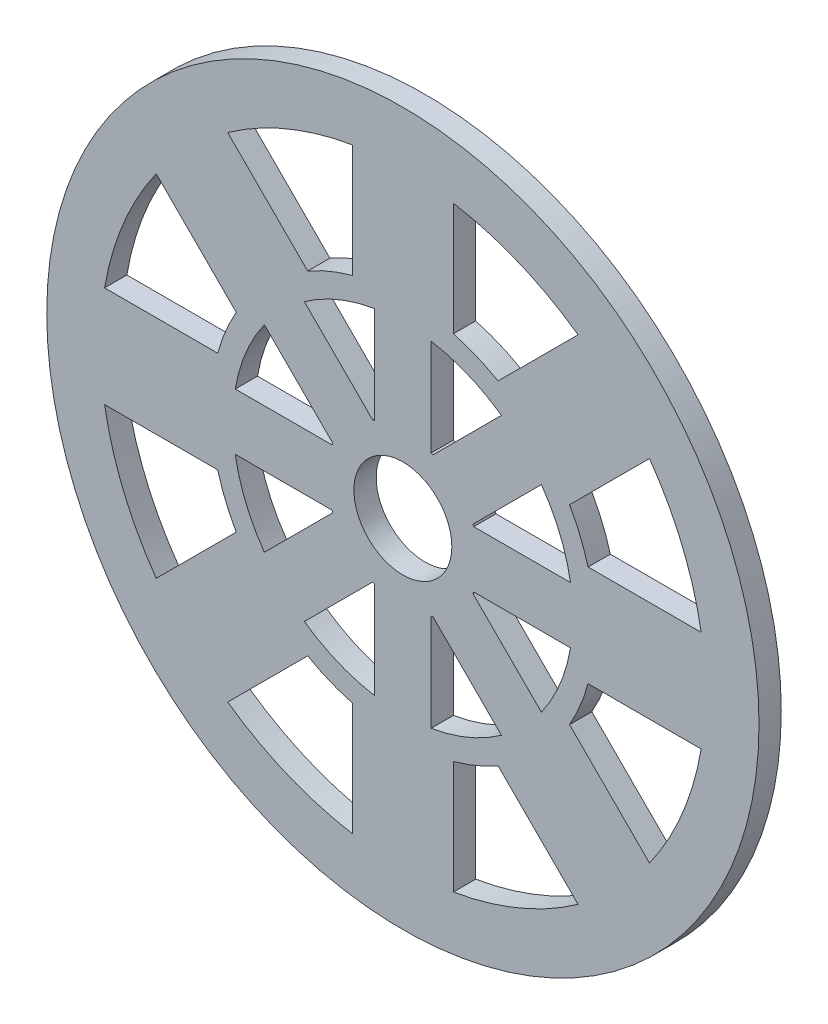
SolidWorks part; units mm, degrees
ref_plane "Front Plane" through (0, 0, 0) normal (0, 0, 1) x (1, 0, 0)
ref_plane "Top Plane" through (0, 0, 0) normal (0, 1, 0) x (1, 0, 0)
ref_plane "Right Plane" through (0, 0, 0) normal (1, 0, 0) x (0, 0, -1)
sketch "Sketch1" plane through (0, 0, 0) normal (0, 0, 1) x (1, 0, 0)
  line L0 (0, 80) -> (0, -80) construction
  line L1 (80, 0) -> (-80, 0) construction
  line L2 (33.9058, -24.9255) -> (51.8663, -42.886)
  line L3 (41.6, -6.35) -> (67, -6.35)
  line L4 (41.6, -6.35) -> (41.6, 6.35)
  line L5 (41.6, 6.35) -> (67, 6.35)
  line L6 (67, -6.35) -> (67, 6.35)
  line L7 (42.886, -51.8663) -> (51.8663, -42.886)
  line L8 (24.9255, -33.9058) -> (42.886, -51.8663)
  line L9 (24.9255, -33.9058) -> (33.9058, -24.9255)
  line L10 (6.35, -41.6) -> (6.35, -67)
  line L11 (-6.35, -67) -> (6.35, -67)
  line L12 (-6.35, -41.6) -> (-6.35, -67)
  line L13 (-6.35, -41.6) -> (6.35, -41.6)
  line L14 (-24.9255, -33.9058) -> (-42.886, -51.8663)
  line L15 (-51.8663, -42.886) -> (-42.886, -51.8663)
  line L16 (-33.9058, -24.9255) -> (-51.8663, -42.886)
  line L17 (-33.9058, -24.9255) -> (-24.9255, -33.9058)
  line L18 (-41.6, -6.35) -> (-67, -6.35)
  line L19 (-67, 6.35) -> (-67, -6.35)
  line L20 (-41.6, 6.35) -> (-67, 6.35)
  line L21 (-41.6, 6.35) -> (-41.6, -6.35)
  line L22 (-33.9058, 24.9255) -> (-51.8663, 42.886)
  line L23 (-42.886, 51.8663) -> (-51.8663, 42.886)
  line L24 (-24.9255, 33.9058) -> (-42.886, 51.8663)
  line L25 (-24.9255, 33.9058) -> (-33.9058, 24.9255)
  line L26 (-6.35, 41.6) -> (-6.35, 67)
  line L27 (6.35, 67) -> (-6.35, 67)
  line L28 (6.35, 41.6) -> (6.35, 67)
  line L29 (6.35, 41.6) -> (-6.35, 41.6)
  line L30 (24.9255, 33.9058) -> (42.886, 51.8663)
  line L31 (51.8663, 42.886) -> (42.886, 51.8663)
  line L32 (33.9058, 24.9255) -> (51.8663, 42.886)
  line L33 (33.9058, 24.9255) -> (24.9255, 33.9058)
  circle A0 centre (0, 0) radius 80
  circle A1 centre (0, 0) radius 11
  point P42 (0, 0)
  dimension "D1" = 160
  dimension "D9" = 22
  dimension "D2" = 12.7
  dimension "D3" = 25.4
  dimension "D4" = 6.35
  dimension "D5" = 13
  dimension "D7" = 13
  dimension "D8" = 6.35
  dimension "D10" = 41.6
  dimension "D6" = 8
extrude "Boss-Extrude1" add sketch "Sketch1" along normal blind 5 contours L21 L20 L19 L18 | A0 A1 L32 L33 L30 L31 L28 L29 L26 L27 L24 L25 L22 L23 L20 L21 L18 L19 L16 L17 L14 L15 L12 L13 L10 L11 L8 L9 L2 L7 L6 L3 L4 L5 | L25 L24 L23 L22 | L29 L28 L27 L26 | L33 L32 L31 L30 | L3 L6 L5 L4 | L9 L8 L7 L2 | L13 L12 L11 L10 | L17 L16 L15 L14 region at (38.3959, -38.3959, 0) region at (54.3, 0, 0) region at (0, -54.3, 0) region at (-38.3959, -38.3959, 0) region at (-54.3, 0, 0) region at (-38.3959, 38.3959, 0) region at (0, 54.3, 0) region at (38.3959, 38.3959, 0) region at (-77.7373, 0, 0)
extrude "Cut-Extrude2" cut sketch "Sketch1<3>" along normal blind 3.175 contours L26 L27 L28 L29 | L24 L23 L22 L25 | L32 L31 L30 L33 | L5 L6 L3 L4 | L20 L19 L18 L21 | L14 L15 L16 L17 | L12 L11 L10 L13 | L8 L7 L2 L9
sketch "Sketch1<3>" plane through (0, 0, 0) normal (0, 0, 1) x (1, 0, 0) same geometry as "Sketch1"
sketch "Sketch2" plane through (0, 0, 0) normal (0, 0, -1) x (-1, 0, 0)
  line L0 (37.6554, -6.35) -> (15.9112, -6.35)
  line L1 (-6.35, 37.6554) -> (-6.35, 15.9112)
  line L2 (6.35, 37.6554) -> (6.35, 15.9112)
  line L3 (37.6554, 6.35) -> (15.9112, 6.35)
  line L4 (22.1363, 31.1165) -> (6.7608, 15.7411)
  line L5 (31.1165, 22.1363) -> (15.7411, 6.7608)
  line L6 (24.9255, 33.9058) -> (33.9058, 24.9255) construction
  line L7 (31.1165, -22.1363) -> (15.7411, -6.7608)
  line L8 (22.1363, -31.1165) -> (6.7608, -15.7411)
  line L9 (-6.35, -37.6554) -> (-6.35, -15.9112)
  line L10 (6.35, -37.6554) -> (6.35, -15.9112)
  line L11 (-22.1363, -31.1165) -> (-6.7608, -15.7411)
  line L12 (-31.1165, -22.1363) -> (-15.7411, -6.7608)
  line L13 (-37.6554, -6.35) -> (-15.9112, -6.35)
  line L14 (-37.6554, 6.35) -> (-15.9112, 6.35)
  line L15 (-31.1165, 22.1363) -> (-15.7411, 6.7608)
  line L16 (-22.1363, 31.1165) -> (-6.7608, 15.7411)
  circle A0 centre (0, 0) radius 38.187
  circle A1 centre (0, 0) radius 17.1315
  dimension "D1" = 90
  dimension "D2" = 90
extrude "Cut-Extrude3" cut sketch "Sketch2" against normal blind 19 contours A1 L7 A0 L0 | A1 L3 A0 L5 | A1 L4 A0 L2 | A1 L1 A0 L16 | A1 L15 A0 L14 | A1 L13 A0 L12 | A1 L11 A0 L9 | A1 L10 A0 L8 region at (-28.4383, -11.7795, 0) region at (-11.7795, -28.4383, 0) region at (-28.4383, 11.7795, 0) region at (11.7795, -28.4383, 0) region at (-11.7795, 28.4383, 0) region at (28.4383, -11.7795, 0) region at (11.7795, 28.4383, 0) region at (28.4383, 11.7795, 0)
sketch "Sketch3" plane through (0, 0, 0) normal (0, 0, -1) x (-1, 0, 0)
  line L0 (33.9058, 24.9255) -> (51.8663, 42.886) construction
  line L1 (41.6, 6.35) -> (67, 6.35) construction
  line L2 (33.2079, 24.2276) -> (51.8663, 42.886)
  line L3 (41.6, 6.35) -> (67, 6.35)
  line L4 (21.39, -37.4413) -> (39.3505, -55.4018)
  line L5 (37.4413, 21.39) -> (55.4018, 39.3505)
  line L6 (41.6, 11.35) -> (67, 11.35)
  line L7 (11.35, -41.6) -> (11.35, -67)
  line L8 (-37.4413, -21.39) -> (-55.4018, -39.3505)
  line L9 (-41.6, -11.35) -> (-67, -11.35)
  line L10 (-21.39, 37.4413) -> (-39.3505, 55.4018)
  line L11 (-11.35, 41.6) -> (-11.35, 67)
  line L12 (33.9058, -24.9255) -> (51.8663, -42.886) construction
  line L13 (41.6, -6.35) -> (67, -6.35) construction
  line L14 (33.9058, -24.9255) -> (51.8663, -42.886)
  line L15 (41.6, -6.35) -> (67, -6.35)
  line L16 (33.9058, 24.9255) -> (51.8663, 42.886) construction
  line L17 (41.6, -11.35) -> (67, -11.35)
  line L18 (37.4413, -21.39) -> (55.4018, -39.3505)
  line L20 (-11.35, -41.6) -> (-11.35, -67)
  line L21 (-21.39, -37.4413) -> (-39.3505, -55.4018)
  line L22 (-41.6, 11.35) -> (-67, 11.35)
  line L23 (-37.4413, 21.39) -> (-55.4018, 39.3505)
  line L24 (11.35, 41.6) -> (11.35, 67)
  line L25 (21.39, 37.4413) -> (39.3505, 55.4018)
  arc A0 (41.6, 11.35) -> (37.4413, 21.39) centre (0, 0) ccw
  arc A1 (67, 11.35) -> (55.4018, 39.3505) centre (0, 0) ccw
  arc A2 (11.35, -41.6) -> (21.39, -37.4413) centre (0, 0) ccw
  arc A3 (11.35, -67) -> (39.3505, -55.4018) centre (0, 0) ccw
  arc A4 (-41.6, -11.35) -> (-37.4413, -21.39) centre (0, 0) ccw
  arc A5 (-67, -11.35) -> (-55.4018, -39.3505) centre (0, 0) ccw
  arc A6 (-11.35, 41.6) -> (-21.39, 37.4413) centre (0, 0) ccw
  arc A7 (-11.35, 67) -> (-39.3505, 55.4018) centre (0, 0) ccw
  arc A8 (41.6, 11.35) -> (37.4413, 21.39) centre (0, 0) ccw
  arc A9 (37.4413, -21.39) -> (41.6, -11.35) centre (0, 0) ccw
  arc A10 (11.35, -41.6) -> (21.39, -37.4413) centre (0, 0) ccw
  arc A11 (-41.6, -11.35) -> (-37.4413, -21.39) centre (0, 0) ccw
  arc A12 (67, 11.35) -> (55.4018, 39.3505) centre (0, 0) ccw
  arc A13 (55.4018, -39.3505) -> (67, -11.35) centre (0, 0) ccw
  arc A14 (11.35, -67) -> (39.3505, -55.4018) centre (0, 0) ccw
  arc A15 (-67, -11.35) -> (-55.4018, -39.3505) centre (0, 0) ccw
  arc A16 (-11.35, 67) -> (-39.3505, 55.4018) centre (0, 0) ccw
  arc A17 (-21.39, -37.4413) -> (-11.35, -41.6) centre (0, 0) ccw
  arc A18 (-39.3505, -55.4018) -> (-11.35, -67) centre (0, 0) ccw
  arc A19 (-37.4413, 21.39) -> (-41.6, 11.35) centre (0, 0) ccw
  arc A20 (-55.4018, 39.3505) -> (-67, 11.35) centre (0, 0) ccw
  arc A21 (21.39, 37.4413) -> (11.35, 41.6) centre (0, 0) ccw
  arc A22 (39.3505, 55.4018) -> (11.35, 67) centre (0, 0) ccw
  point P25 (0, 0)
  point P47 (0, 0)
  dimension "D3" = 4
  dimension "D1" = 4
  dimension "D2" = 5
extrude "Cut-Extrude4" cut sketch "Sketch3" against normal blind 19 contours L21 A18 L20 A17 | L9 A5 L8 A4 | L23 A20 L22 A19 | L11 A7 L10 A6 | L25 A22 L24 A21 | L6 A1 L5 A0 | L18 A13 L17 A9 | L7 A3 L4 A2 region at (-21.8638, -52.7839, 0) region at (-52.7839, 21.8638, 0) region at (52.7839, -21.8638, 0) region at (21.8638, 52.7839, 0) region at (-52.7839, -21.8638, 0) region at (21.8638, -52.7839, 0) region at (52.7839, 21.8638, 0) region at (-21.8638, 52.7839, 0)
